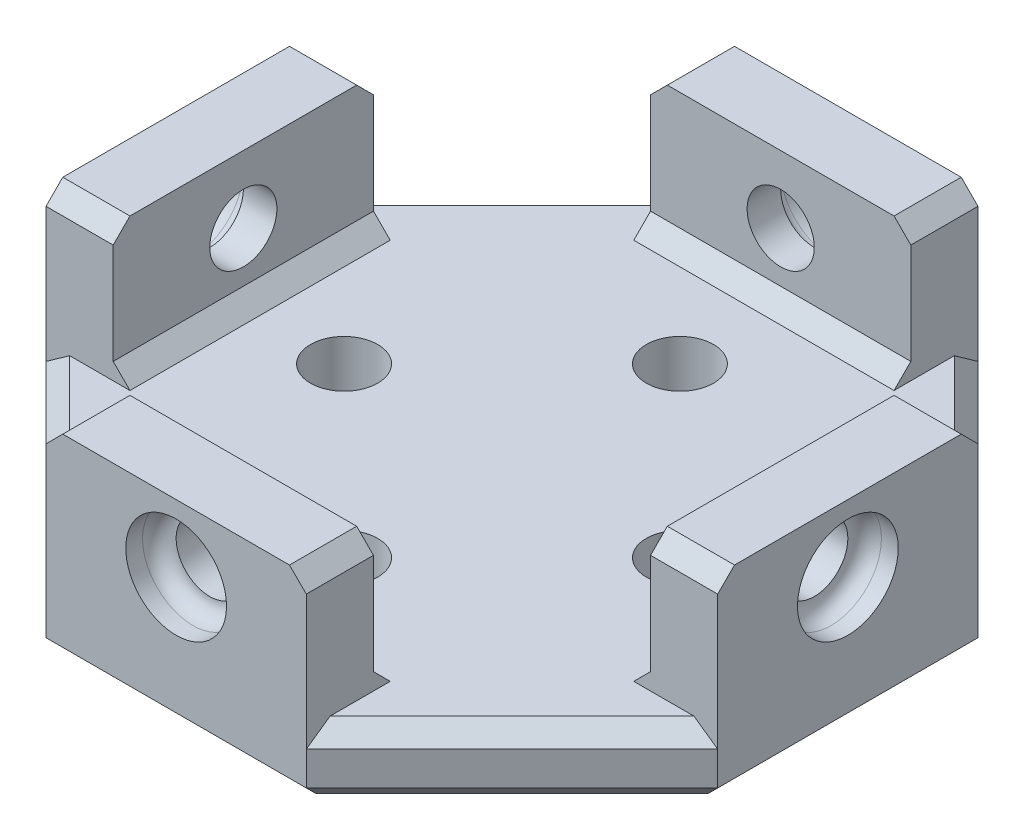
SolidWorks part; units mm, degrees
ref_plane "Front Plane" through (0, 0, 0) normal (0, 0, 1) x (1, 0, 0)
ref_plane "Top Plane" through (0, 0, 0) normal (0, 1, 0) x (1, 0, 0)
ref_plane "Right Plane" through (0, 0, 0) normal (1, 0, 0) x (0, 0, -1)
sketch "Sketch1" plane through (0, 0, 0) normal (0, 1, 0) x (1, 0, 0)
  line L1 (-20, 20) -> (20, 20)
  line L2 (-20, 20) -> (-20, -20)
  line L3 (-20, -20) -> (20, -20)
  line L4 (20, 20) -> (20, -20)
  line L5 (-20, 20) -> (20, -20) construction
  line L6 (-20, -20) -> (20, 20) construction
  point P0 (0, 0)
  dimension "D1" = 40
  dimension "D2" = 40
extrude "Boss-Extrude1" add sketch "Sketch1" along normal blind 4
sketch "Sketch2" plane through (0, 4, 0) normal (0, 1, 0) x (1, 0, 0)
  line L0 (0, 0) -> (-10, 0) construction
  circle A0 centre (-10, 0) radius 2
  circle A1 centre (0, 10) radius 2
  circle A2 centre (10, 0) radius 2
  circle A3 centre (0, -10) radius 2
  point P13 (0, 0)
  dimension "D2" = 4
  dimension "D1" = 10
  dimension "D3" = 4
extrude "Cut-Extrude1" cut sketch "Sketch2" against normal through all
sketch "Sketch3" plane through (0, 4, 0) normal (0, 1, 0) x (1, 0, 0)
  line L0 (0, 20) -> (0, -20) construction
  line L1 (20, 20) -> (-20, 20) construction
  line L2 (-20, -20) -> (20, -20) construction
  line L3 (-20, 0) -> (20, 0) construction
  line L4 (-20, 20) -> (-20, -20) construction
  line L5 (20, -20) -> (20, 20) construction
  line L7 (-7.75, 20) -> (-20, 20)
  line L9 (20, 7.75) -> (20, 20)
  line L10 (-20, 7.75) -> (-7.75, 20)
  line L11 (7.75, 20) -> (20, 7.75)
  line L12 (20, -7.75) -> (7.75, -20)
  line L13 (-20, -7.75) -> (-7.75, -20)
  line L14 (20, -20) -> (20, 20)
  line L15 (20, 20) -> (-20, 20)
  line L16 (-20, 20) -> (-20, -20)
  line L17 (-20, -20) -> (20, -20)
  line L18 (20, -20) -> (20, -7.75)
  line L19 (20, 20) -> (7.75, 20)
  line L20 (-20, 20) -> (-20, 7.75)
  line L21 (-20, -20) -> (-7.75, -20)
  line L22 (-20, -7.75) -> (-20, -20)
  line L23 (7.75, -20) -> (20, -20)
  point P24 (0, 0)
  point P25 (0, 0)
  dimension "D1" = 15.5
  dimension "D3" = 0
extrude "Cut-Extrude2" cut sketch "Sketch3" against normal through all
sketch "Sketch4" plane through (0, 4, 0) normal (0, 1, 0) x (1, 0, 0)
  line L0 (0, 20) -> (0, 16) construction
  line L1 (7.75, 20) -> (-7.75, 20) construction
  line L2 (16, 7.75) -> (20, -7.75) construction
  line L3 (-7.75, 16) -> (7.75, 16)
  line L4 (-7.75, 16) -> (-7.75, 20)
  line L5 (-7.75, 20) -> (7.75, 20)
  line L6 (7.75, 16) -> (7.75, 20)
  line L7 (-7.75, 16) -> (7.75, 20) construction
  line L8 (-7.75, 20) -> (7.75, 16) construction
  line L9 (20, 7.75) -> (16, -7.75) construction
  line L10 (16, 7.75) -> (20, 7.75)
  line L11 (16, 7.75) -> (16, -7.75)
  line L12 (16, -7.75) -> (20, -7.75)
  line L13 (20, 7.75) -> (20, -7.75)
  line L14 (7.75, -16) -> (-7.75, -20) construction
  line L15 (7.75, -20) -> (-7.75, -16) construction
  line L16 (7.75, -16) -> (7.75, -20)
  line L17 (7.75, -16) -> (-7.75, -16)
  line L18 (-7.75, -16) -> (-7.75, -20)
  line L19 (7.75, -20) -> (-7.75, -20)
  line L20 (-16, -7.75) -> (-20, 7.75) construction
  line L21 (-20, -7.75) -> (-16, 7.75) construction
  line L22 (-16, -7.75) -> (-20, -7.75)
  line L23 (-16, -7.75) -> (-16, 7.75)
  line L24 (-16, 7.75) -> (-20, 7.75)
  line L25 (-20, -7.75) -> (-20, 7.75)
  point P5 (0, 18)
  point P14 (18, 0)
  point P19 (0, -18)
  point P24 (-18, 0)
  point P29 (0, 0)
  dimension "D1" = 4
  dimension "D2" = 4
extrude "Boss-Extrude2" add sketch "Sketch4" along normal blind 8
sketch "Sketch5" plane through (16, 0, 0) normal (-1, 0, 0) x (0, 0, 1)
  line L0 (-7.75, 4) -> (7.75, 12) construction
  line L1 (-7.75, 12) -> (7.75, 4) construction
  circle A0 centre (0, 8) radius 2
  dimension "D1" = 4
extrude "Cut-Extrude3" cut sketch "Sketch5" against normal blind 5 and the other way through all
sketch "Sketch6" plane through (0, 0, 16) normal (0, 0, -1) x (-1, 0, 0)
  line L0 (-7.75, 12) -> (7.75, 4) construction
  line L3 (7.75, 12) -> (-7.75, 4) construction
  circle A0 centre (0, 8) radius 2
  dimension "D1" = 4
extrude "Cut-Extrude4" cut sketch "Sketch6" against normal blind 5 and the other way through all
sketch "Sketch7" plane through (0, 0, 20) normal (0, 0, 1) x (1, 0, 0)
  circle A0 centre (0, 8) radius 3
  dimension "D1" = 6
extrude "Cut-Extrude5" cut sketch "Sketch7" against normal blind 2
sketch "Sketch9" plane through (0, 0, 0) normal (1, 0, 0) x (0, 0, -1)
  line L0 (0, -4.8173) -> (0, 19.0183) construction
pattern_circular "CirPattern1" count 4 every 90 about axis through (0, -4.8173, 0) along (0, 1, 0) of "Cut-Extrude5"
chamfer "Chamfer1" distance 1 angle 45 16 edges at (13.875, 0, 13.875) (20, 0, 0) (13.875, 0, -13.875) (0, 0, -20) (-13.875, 0, -13.875) (-20, 0, 0) (-13.875, 0, 13.875) (0, 0, 20) (-18, 12, 7.75) (-18, 12, -7.75) (-7.75, 12, -18) (7.75, 12, -18) (18, 12, -7.75) (18, 12, 7.75) (7.75, 12, 18) (-7.75, 12, 18)
fillet "Fillet1" radius 1 4 edges at (18, 8, -3) (-3, 8, -18) (-18, 8, 3) (3, 8, 18)
chamfer "Chamfer2" distance 1 angle 45 8 edges at (-13.875, 4, -13.875) (13.875, 4, -13.875) (13.875, 4, 13.875) (-13.875, 4, 13.875) (16, 4, 0) (0, 4, -16) (-16, 4, 0) (0, 4, 16)
